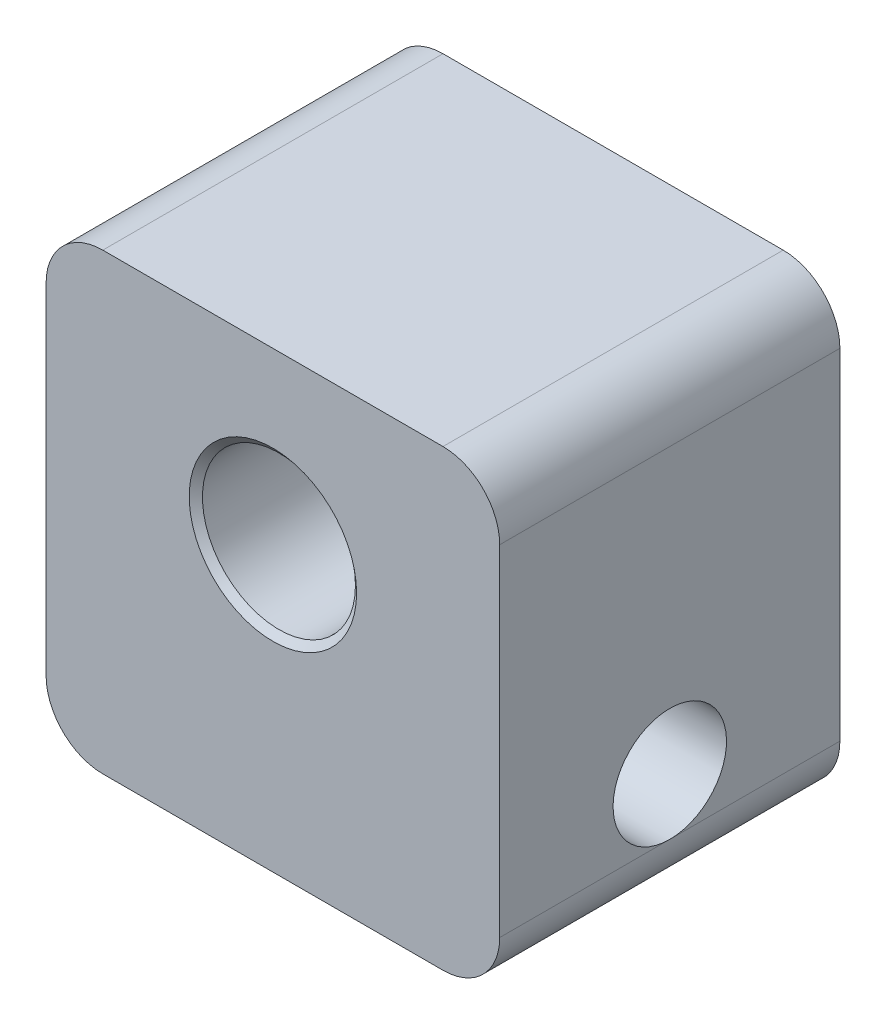
SolidWorks part; units mm, degrees
ref_plane "Front Plane" through (0, 0, 0) normal (0, 0, 1) x (1, 0, 0)
ref_plane "Top Plane" through (0, 0, 0) normal (0, 1, 0) x (1, 0, 0)
ref_plane "Right Plane" through (0, 0, 0) normal (1, 0, 0) x (0, 0, -1)
sketch "Sketch1" plane through (0, 0, 0) normal (0, 1, 0) x (1, 0, 0)
  line L1 (-20, 15) -> (20, 15)
  line L2 (-20, 15) -> (-20, -15)
  line L3 (-20, -15) -> (20, -15)
  line L4 (20, 15) -> (20, -15)
  line L5 (-20, 15) -> (20, -15) construction
  line L6 (-20, -15) -> (20, 15) construction
  point P0 (0, 0)
  dimension "D1" = 40
  dimension "D2" = 30
extrude "Boss-Extrude1" add sketch "Sketch1" along normal blind 40
hole_wizard "1/2 Clearance Hole1" positions "Sketch2" profile "Sketch3" hole size "1/2" standard "ANSI Inch" end condition up to next
sketch "Sketch2" plane through (0, 0, 15) normal (0, 0, 1) x (1, 0, 0)
  line L0 (-20, 40) -> (20, 40) construction
  point P0 (0, 25)
  point P3 (0, 0)
  dimension "D1" = 15
sketch "Sketch3" plane through (0, 25, 15) normal (1, 0, 0) x (0, -1, 0)
  line L0 (0, 0) -> (0, 30)
  line L1 (0, 30) -> (6.7462, 30)
  line L2 (6.7462, 30) -> (6.7462, 0.5328)
  line L3 (6.7462, 0.5328) -> (7.3812, 0)
  line L5 (7.3812, 0) -> (0, 0)
  line L6 (-6.7462, 0.5328) -> (-7.3812, 0) construction
  line L11 (0, -6.35) -> (0, 107.95) construction
  dimension "Thru Hole Dia." = 13.4925
  dimension "Thru Hole Depth" = 30
  dimension "Near C'Sink Dia." = 14.7625
  dimension "Near C'Sink Angle" = 100
sketch "Sketch4" plane through (20, 0, 0) normal (1, 0, 0) x (0, 0, -1)
  line L0 (-15, 0) -> (15, 0) construction
  circle A0 centre (0, 10) radius 5
  point P4 (0, 0)
  dimension "D1" = 10
  dimension "D2" = 10
extrude "Cut-Extrude1" cut sketch "Sketch4" against normal up to next
fillet "Fillet1" radius 5 5 edges at (6.7462, 25, -15) (20, 0, 0) (-20, 0, 0) (-20, 40, 0) (20, 40, 0)
